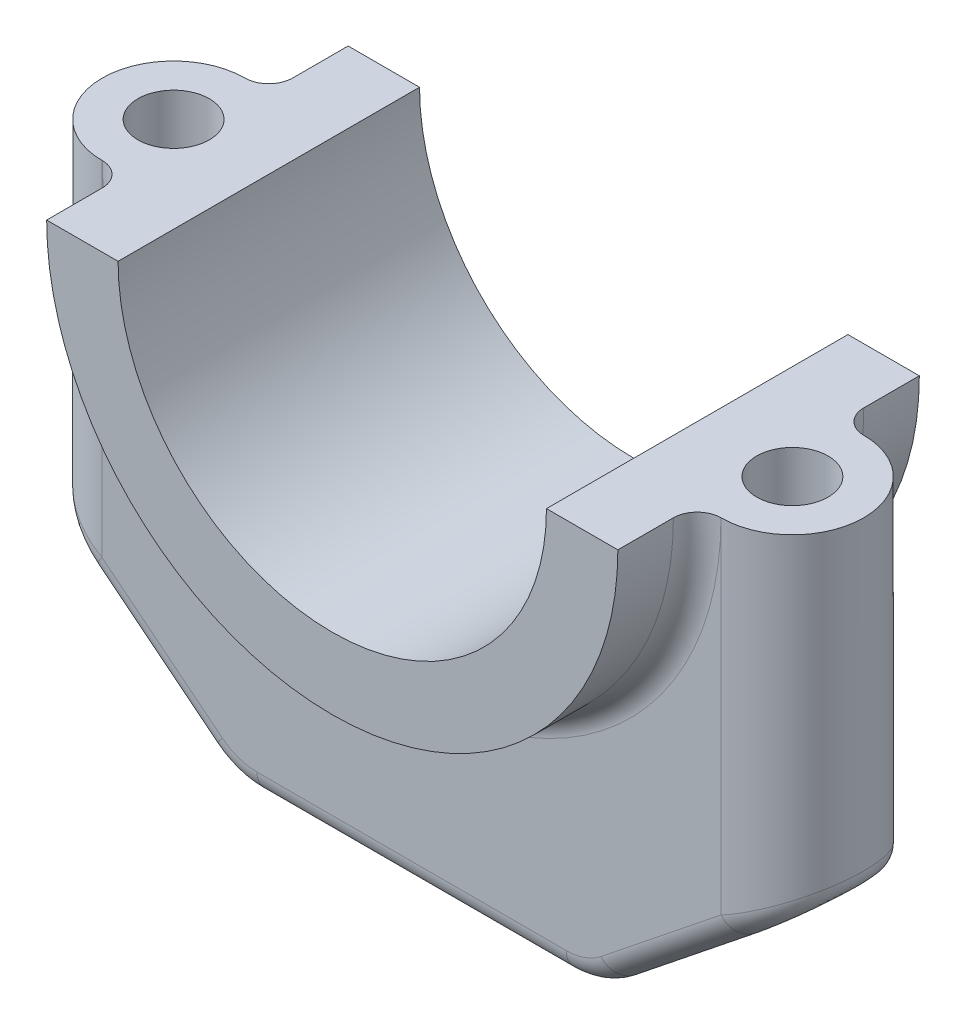
SolidWorks part; units mm, degrees
ref_plane "Front Plane" through (0, 0, 0) normal (0, 0, 1) x (1, 0, 0)
ref_plane "Top Plane" through (0, 0, 0) normal (0, 1, 0) x (1, 0, 0)
ref_plane "Right Plane" through (0, 0, 0) normal (1, 0, 0) x (0, 0, -1)
sketch "Sketch1" plane through (0, 0, 0) normal (0, 0, 1) x (1, 0, 0)
  line L4 (0, 55.8258) -> (0, -90.9163) construction
  line L9 (-36, 0) -> (64.2953, 0) construction
  line L10 (-36, 0) -> (-27, 0)
  line L11 (27, 0) -> (36, 0)
  line L12 (-36, 0) -> (-27, 0)
  arc A0 (-27, 0) -> (27, 0) centre (0, 0) ccw
  arc A1 (-36, 0) -> (36, 0) centre (0, 0) ccw
  dimension "D2" = 72
  dimension "D3" = 54
extrude "Boss-Extrude1" add sketch "Sketch1" along normal mid plane 38 contours L10 A1 L11 A0 region at (-31.5, -0.805, 0)
sketch "Sketch3" plane through (0, 0, 0) normal (0, 1, 0) x (1, 0, 0)
  line L0 (-39, 0) -> (39, 0) construction
  line L1 (-39, 9) -> (39, 9)
  line L2 (-39, -9) -> (39, -9)
  arc A0 (-39, 9) -> (-39, -9) centre (-39, 0) ccw
  arc A1 (39, -9) -> (39, 9) centre (39, 0) ccw
  point P3 (0, 0)
  dimension "D3" = 9
  dimension "D1" = 78
  dimension "D2" = 39
extrude "Boss-Extrude2" add sketch "Sketch3" against normal blind 60
sketch "Sketch4" plane through (0, 0, 0) normal (0, 1, 0) x (1, 0, 0)
  circle A0 centre (-39, 0) radius 4.5
  circle A1 centre (39, 0) radius 4.5
extrude "Cut-Extrude1" cut sketch "Sketch4" against normal blind 60
sketch "Sketch5" plane through (0, 0, 9) normal (0, 0, 1) x (1, 0, 0)
  line L0 (-48, -40) -> (-23, -60)
  line L1 (-48, 0) -> (-48, -60) construction
  line L2 (-39, -60) -> (39, -60) construction
  line L3 (-23, -60) -> (-48, -60)
  line L4 (-48, -60) -> (-48, -40)
  line L5 (48, -40) -> (23, -60)
  line L6 (48, -60) -> (48, 0) construction
  line L7 (23, -60) -> (48, -60)
  line L8 (48, -60) -> (48, -40)
  dimension "D1" = 20
  dimension "D2" = 25
  dimension "D3" = 25
  dimension "D4" = 20
extrude "Cut-Extrude2" cut sketch "Sketch5" against normal blind 60
fillet "Fillet1" radius 10 2 edges at (23, -60, 0) (-23, -60, 0)
fillet "Fillet2" radius 3 14 edges at (22.8023, -59.4363, -9) (32.3696, -52.5043, -9) (48, -40, 0) (32.3696, -52.5043, 9) (22.8023, -59.4363, 9) (0, -60, 9) (-22.8023, -59.4363, 9) (-32.3696, -52.5043, 9) (-48, -40, 0) (-32.3696, -52.5043, -9) (-22.8023, -59.4363, -9) (0, -60, -9) (0, -36, -9) (0, -36, 9)
sketch "Sketch6" plane through (0, 0, -9) normal (0, 0, -1) x (-1, 0, 0)
  line L0 (-27, 0) -> (27, 0) construction
  line L1 (-27, 0) -> (27, 0)
  arc A0 (-27, 0) -> (27, 0) centre (0, 0) ccw construction
  arc A1 (-27, 0) -> (27, 0) centre (0, 0) ccw
extrude "Cut-Extrude3" cut sketch "Sketch6" against normal blind 60
